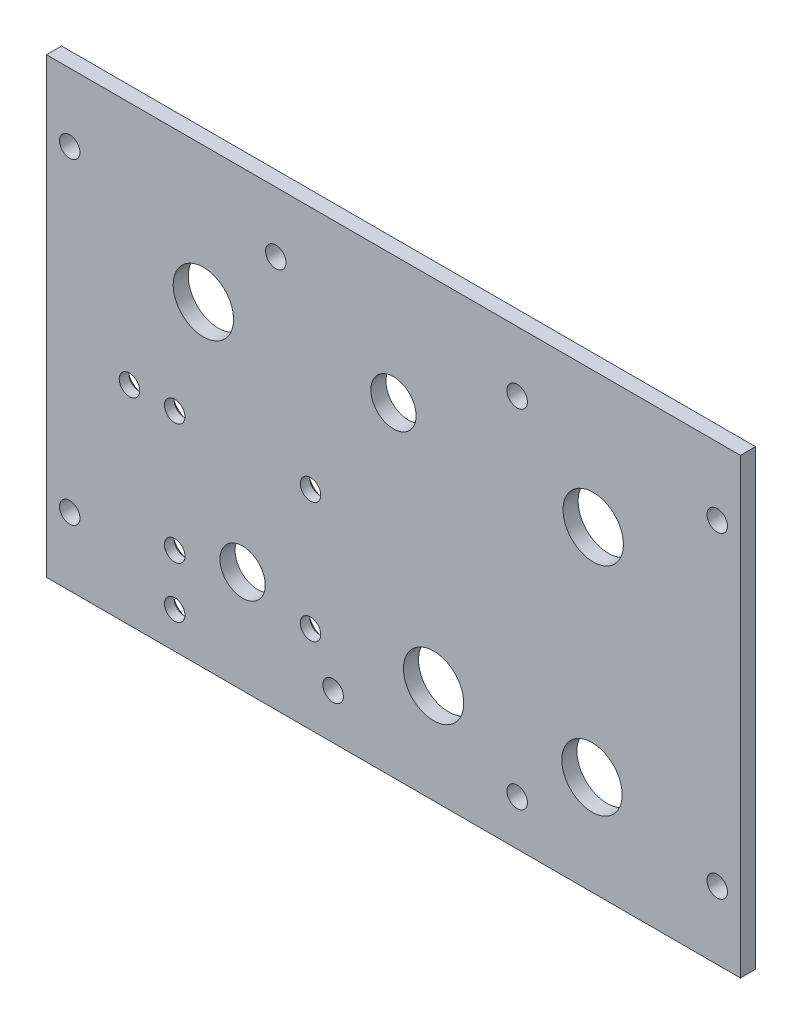
SolidWorks part; units mm, degrees
material "Acrylic (Medium-high impact)"
ref_plane "Front Plane" through (0, 0, 0) normal (0, 0, 1) x (1, 0, 0)
ref_plane "Top Plane" through (0, 0, 0) normal (0, 1, 0) x (1, 0, 0)
ref_plane "Right Plane" through (0, 0, 0) normal (1, 0, 0) x (0, 0, -1)
sketch "Sketch1" plane through (0, 0, 0) normal (0, 0, 1) x (1, 0, 0)
  line L8 (0, 95.25) -> (-146.05, 95.25)
  line L9 (-146.05, 95.25) -> (-146.05, 0)
  line L10 (-146.05, 0) -> (0, 0)
  line L11 (0, 0) -> (0, 95.25)
extrude "Boss-Extrude1" add sketch "Sketch1" against normal blind 3.175
hole_wizard "#6 Clearance Hole1" positions "Sketch3" profile "Sketch2" hole size "#6" standard "ANSI Inch" end condition through all
sketch "Sketch3" plane through (0, 0, -3.175) normal (0, 0, -1) x (-1, 0, 0)
  point P0 (4.8895, 80.9625)
  point P3 (141.1605, 80.9625)
  point P6 (141.1605, 14.2875)
  point P9 (4.8895, 14.2875)
  point P12 (46.99, 9.525)
  point P15 (85.725, 9.525)
  point P18 (97.79, 82.55)
  point P21 (46.99, 82.55)
sketch "Sketch2" plane through (-4.8895, 80.9625, -3.175) normal (1, 0, 0) x (0, 1, 0)
  line L0 (0, 0) -> (0, 3.175)
  line L1 (0, 3.175) -> (2.1526, 3.175)
  line L2 (2.1526, 3.175) -> (2.1526, 0)
  line L5 (2.1526, 0) -> (0, 0)
  line L11 (0, -6.35) -> (0, 107.95) construction
  dimension "Thru Hole Dia." = 4.3053
  dimension "Thru Hole Depth" = 3.175
sketch "Sketch5" plane through (0, 0, -7.4676) normal (0, 0, -1) x (-1, 0, 0)
  circle A0 centre (30.988, 66.675) radius 6.35
  circle A1 centre (113.03, 66.675) radius 6.35
  circle A2 centre (64.5795, 20.955) radius 6.35
  circle A3 centre (31.242, 20.955) radius 6.35
  circle A4 centre (73.025, 68.326) radius 4.7625
  circle A5 centre (104.775, 21.59) radius 4.7625
  dimension "D1" = 12.7
  dimension "D2" = 9.525
extrude "Cut-Extrude1" cut sketch "Sketch5" against normal through all
hole_wizard "CSK for #6 Flat Head Machine Screw (100)1" positions "Sketch7" profile "Sketch6" countersink size "#6" standard "ANSI Inch" end condition through all
sketch "Sketch7" plane through (0, 0, -3.175) normal (0, 0, -1) x (-1, 0, 0)
  point P0 (90.4875, 43.815)
  point P3 (90.4875, 18.415)
  point P6 (119.0625, 7.6362)
  point P9 (119.0625, 18.415)
  point P12 (119.0625, 43.815)
  point P15 (128.5875, 43.815)
sketch "Sketch6" plane through (-90.4875, 43.815, -3.175) normal (1, 0, 0) x (0, 1, 0)
  line L0 (0, 0) -> (0, 3.175)
  line L1 (0, 3.175) -> (2.1526, 3.175)
  line L2 (2.1526, 3.175) -> (2.1526, 1.1669)
  line L3 (2.1526, 1.1669) -> (3.5433, 0)
  line L5 (3.5433, 0) -> (0, 0)
  line L6 (-2.1526, 1.1669) -> (-3.5433, 0) construction
  line L11 (0, -6.35) -> (0, 107.95) construction
  dimension "Thru Hole Dia." = 4.3053
  dimension "Thru Hole Depth" = 3.175
  dimension "Near C'Sink Dia." = 7.0866
  dimension "Near C'Sink Angle" = 100
